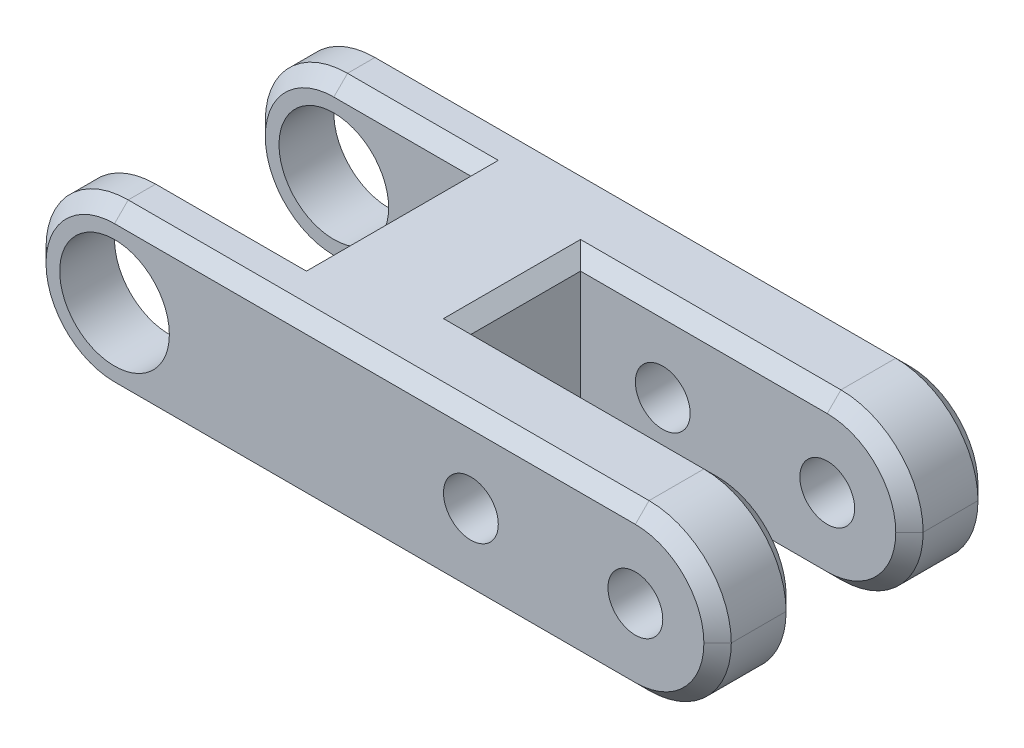
SolidWorks part; units mm, degrees
ref_plane "Front Plane" through (0, 0, 0) normal (0, 0, 1) x (1, 0, 0)
ref_plane "Top Plane" through (0, 0, 0) normal (0, 1, 0) x (1, 0, 0)
ref_plane "Right Plane" through (0, 0, 0) normal (1, 0, 0) x (0, 0, -1)
sketch "Sketch2" plane through (0, 0, 0) normal (0, 1, 0) x (1, 0, 0)
  line L0 (0, 3) -> (0, 5)
  line L1 (0, 5) -> (25, 5)
  line L2 (8, -3) -> (8, 3)
  line L3 (25, -5) -> (0, -5)
  line L4 (0, -5) -> (0, -3)
  line L5 (0, -3) -> (8, -3)
  line L6 (8, 3) -> (0, 3)
  line L7 (25, 5) -> (25, 2)
  line L8 (25, 2) -> (13, 2)
  line L10 (13, -2) -> (25, -2)
  line L11 (25, -2) -> (25, -5)
  line L12 (13, 2) -> (13, -2)
  point P3 (13, 0)
  point P13 (8, 0)
  dimension "D1" = 6
  dimension "D2" = 4
  dimension "D3" = 2
  dimension "D4" = 2
  dimension "D5" = 5
  dimension "D6" = 12
  dimension "D7" = 12
  dimension "D8" = 8
extrude "Boss-Extrude1" add sketch "Sketch2" along normal blind 6
fillet "Fillet1" radius 3 8 edges at (25, 6, -3.5) (25, 0, -3.5) (25, 0, 3.5) (25, 6, 3.5) (0, 6, 4) (0, 0, 4) (0, 0, -4) (0, 6, -4)
sketch "Sketch3" plane through (0, 0, 5) normal (0, 0, 1) x (1, 0, 0)
  line L0 (3, 6) -> (22, 6) construction
  point P0 (3, 3)
  point P1 (22, 3)
  point P2 (16, 3)
  dimension "D1" = 3
  dimension "D2" = 3
  dimension "D3" = 9
  dimension "D4" = 3
hole_wizard "Ø4.0mm Dowel Hole1" positions "Sketch6" profile "Sketch7" hole size "Ø4.0" standard "ISO"
sketch "Sketch6" plane through (0, 0, 5) normal (0, 0, 1) x (1, 0, 0)
  point P0 (3, 3)
sketch "Sketch7" plane through (3, 3, 5) normal (1, 0, 0) x (0, -1, 0)
  line L0 (0, 0) -> (0, 11.2017)
  line L1 (0, 11.2017) -> (2, 10)
  line L2 (2, 10) -> (2, 0)
  line L5 (2, 0) -> (0, 0)
  line L10 (0, 11.2017) -> (-2, 10) construction
  line L11 (0, -6.35) -> (0, 107.95) construction
  dimension "Hole Dia." = 4
  dimension "Hole Depth" = 10
  dimension "Drill Angle" = 118
hole_wizard "Ø2.0mm Dowel Hole1" positions "3DSketch1" profile "Sketch8" hole size "Ø2.0" standard "ISO"
sketch3d "3DSketch1"
  point P0 (16, 3, 5)
  point P3 (22, 3, 5)
sketch "Sketch8" plane through (16, 3, 5) normal (1, 0, 0) x (0, -1, 0)
  line L0 (0, 0) -> (0, 10.6009)
  line L1 (0, 10.6009) -> (1, 10)
  line L2 (1, 10) -> (1, 0)
  line L5 (1, 0) -> (0, 0)
  line L10 (0, 10.6009) -> (-1, 10) construction
  line L11 (0, -6.35) -> (0, 107.95) construction
  dimension "Hole Dia." = 2
  dimension "Hole Depth" = 10
  dimension "Drill Angle" = 118
chamfer "Chamfer1" distance 0.5 angle 45 30 edges at (12.5, 0, 5) (0.8787, 0.8787, 5) (24.1213, 0.8787, 5) (0.8787, 5.1213, 5) (24.1213, 5.1213, 5) (12.5, 6, 5) (5.5, 0, 3) (5.5, 0, -3) (0.8787, 0.8787, 3) (0.8787, 0.8787, -3) (0.8787, 5.1213, 3) (0.8787, 5.1213, -3) (5.5, 6, 3) (8, 6, 0) (5.5, 6, -3) (12.5, 0, -5) (24.1213, 0.8787, -5) (0.8787, 0.8787, -5) (24.1213, 5.1213, -5) (0.8787, 5.1213, -5) (12.5, 6, -5) (17.5, 0, 2) (17.5, 0, -2) (24.1213, 0.8787, 2) (24.1213, 0.8787, -2) (24.1213, 5.1213, 2) (24.1213, 5.1213, -2) (17.5, 6, 2) (13, 6, 0) (17.5, 6, -2)
